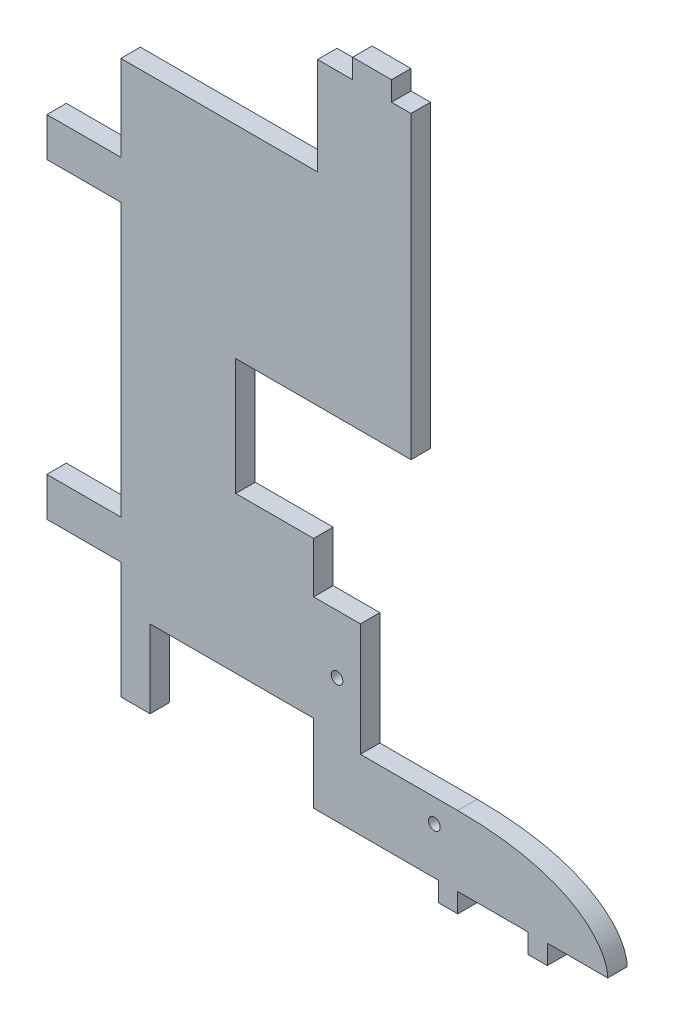
SolidWorks part; units mm, degrees
ref_plane "Plan de face" through (0, 0, 0) normal (0, 0, 1) x (1, 0, 0)
ref_plane "Plan de dessus" through (0, 0, 0) normal (0, 1, 0) x (1, 0, 0)
ref_plane "Plan de droite" through (0, 0, 0) normal (1, 0, 0) x (0, 0, -1)
sketch "Esquisse1" plane through (0, 0, 0) normal (0, 0, 1) x (1, 0, 0)
  line L1 (0, 0) -> (32, 0)
  line L2 (0, 0) -> (0, 47)
  line L3 (0, 47) -> (12, 47)
  line L4 (37, 0) -> (37, 18)
  line L6 (12, 47) -> (12, 18)
  line L7 (12, 18) -> (37, 18)
  line L8 (37, 0) -> (37, -5)
  line L9 (37, -5) -> (32, -5)
  line L10 (32, 0) -> (32, -5)
  circle A0 centre (6, 32) radius 1.5
  circle A1 centre (31, 12) radius 1.5
  dimension "D3" = 20
  dimension "D4" = 3
  dimension "D1" = 6
  dimension "D2" = 12
  dimension "D5" = 15
  dimension "D6" = 6
  dimension "D7" = 25
  dimension "D8" = 6
  dimension "D9" = 6
  dimension "D10" = 5
  dimension "D11" = 5
extrude "Boss.-Extru.1" add sketch "Esquisse1" along normal blind 5
sketch "Esquisse2" plane through (0, 0, 0) normal (0, 0, -1) x (-1, 0, 0)
  line L0 (-37, 18) -> (-12, 18) construction
  line L1 (-37, 0) -> (-55, 0)
  line L2 (-37, 0) -> (-37, 18)
  line L3 (-60, 0) -> (-75.5, 0)
  line L4 (42, 0) -> (49.5, 0)
  line L5 (0, 20) -> (0, 60)
  line L6 (0, 60) -> (20, 60)
  line L7 (-10, 167) -> (-1, 167)
  line L8 (0, 0) -> (-32, 0) construction
  line L9 (20, 60) -> (20, 90)
  line L10 (49.5, 120) -> (49.5, 142)
  line L11 (49.5, 0) -> (49.5, 30)
  line L12 (49.5, 30) -> (68.5, 30)
  line L14 (49.5, 40) -> (68.5, 40)
  line L15 (-60, 0) -> (-60, -5)
  line L16 (-60, -5) -> (-55, -5)
  line L17 (-55, 0) -> (-55, -5)
  line L18 (0, 20) -> (42, 20)
  line L19 (68.5, 30) -> (68.5, 40)
  line L20 (49.5, 120) -> (68.5, 120)
  line L21 (49.5, 40) -> (49.5, 110)
  line L22 (0, 47) -> (0, 0) construction
  line L23 (-20, 167) -> (-20, 172)
  line L24 (-20, 172) -> (-10, 172)
  line L25 (-10, 167) -> (-10, 172)
  line L26 (0, 0) -> (-32, 0) construction
  line L27 (42, 20) -> (42, 0)
  line L28 (49.5, 110) -> (68.5, 110)
  line L29 (-37, -5) -> (-37, 18) construction
  line L30 (-1, 167) -> (-1, 142)
  line L31 (20, 90) -> (-25, 90)
  line L32 (-1, 142) -> (49.5, 142)
  line L33 (-20, 167) -> (-25, 167)
  line L34 (-25, 90) -> (-25, 167)
  line L35 (68.5, 120) -> (68.5, 110)
  spline S0 degree 3 poles (-75.5, 0) (-75.5, 5.9822) (-67.6854, 18) (-37, 18) knots 0 0 0 0 1 1 1 1
  dimension "D1" = 38.5
  dimension "D2" = 20
  dimension "D3" = 167
  dimension "D4" = 49.5
  dimension "D5" = 5
  dimension "D6" = 30
  dimension "D7" = 10
  dimension "D8" = 10
  dimension "D9" = 30
  dimension "D10" = 70
  dimension "D11" = 19
  dimension "D12" = 5
  dimension "D13" = 42
  dimension "D14" = 20
  dimension "D15" = 40
  dimension "D16" = 45
  dimension "D17" = 5
  dimension "D19" = 25
  dimension "D21" = 24
extrude "Boss.-Extru.2" add sketch "Esquisse2" against normal blind 5
